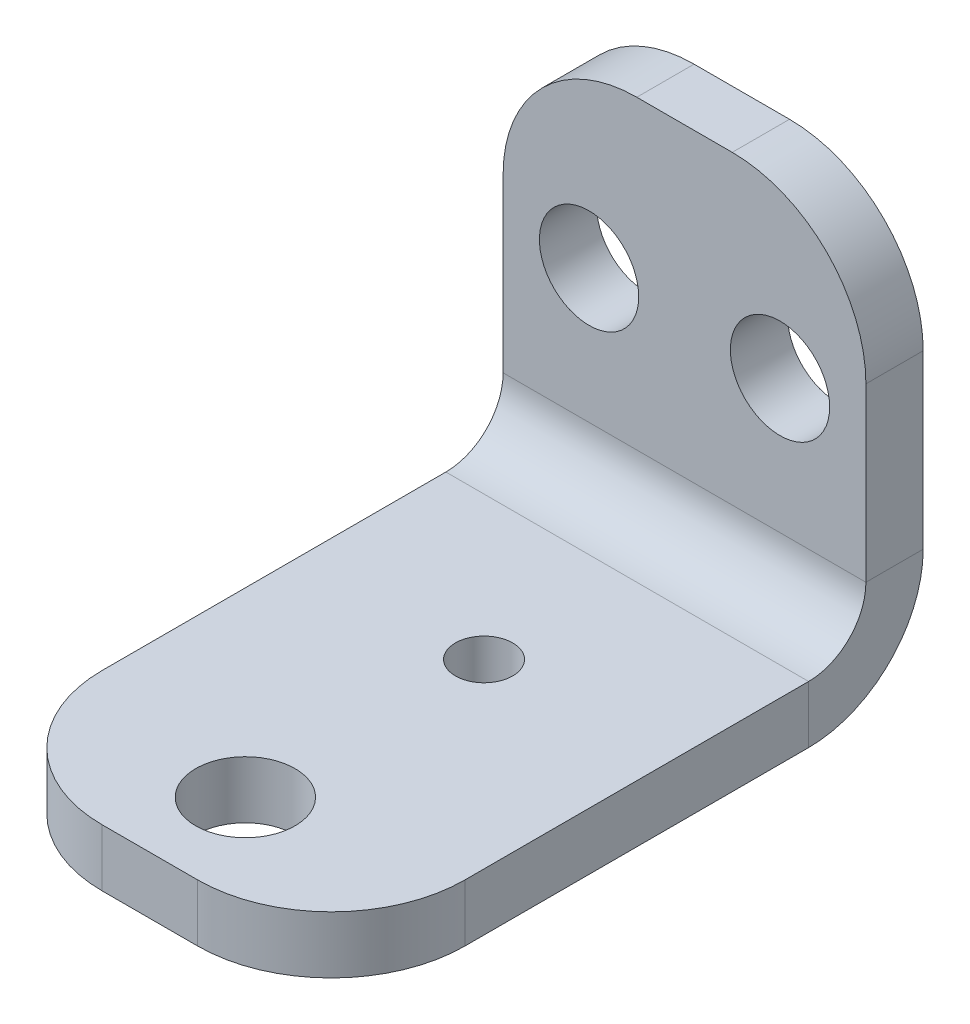
SolidWorks part; units mm, degrees
note: The reader was unsure of these and kept them because the rebuilt part matched: flange length of "Edge-Flange1".
material "AISI 4340 Steel, annealed"
ref_plane "Front Plane" through (0, 0, 0) normal (0, 0, 1) x (1, 0, 0)
ref_plane "Top Plane" through (0, 0, 0) normal (0, 1, 0) x (1, 0, 0)
ref_plane "Right Plane" through (0, 0, 0) normal (1, 0, 0) x (0, 0, -1)
sketch "Sketch1" plane through (0, 0, 0) normal (0, 0, 1) x (1, 0, 0)
  line L1 (-9.5, -11) -> (9.5, -11)
  line L2 (-9.5, -11) -> (-9.5, 11)
  line L3 (-9.5, 11) -> (9.5, 11)
  line L4 (9.5, -11) -> (9.5, 11)
  line L5 (-9.5, -11) -> (9.5, 11) construction
  line L6 (-9.5, 11) -> (9.5, -11) construction
  point P0 (0, 0)
  dimension "D1" = 19
  dimension "D2" = 22
base flange "Base-Flange1" sketch "Sketch1" thickness 3 reverse thickness direction no parameters "D1"=3
edge flange "Edge-Flange1" sketch "Sketch11" flange angle 90 flange length 28 flange position material inside bend radius 3 thickness 3 relief rectangular parameters "D6"=10, "D8"=1
sketch "Sketch11" plane through (0, -11, 0) normal (0, -1, 0) x (1, 0, 0)
  line L0 (-9.5, 0) -> (9.5, 0) construction
  line L1 (-9.5, 0) -> (9.5, 0)
  line L2 (-9.5, 0) -> (-9.5, 28)
  line L3 (-9.5, 28) -> (9.5, 28)
  line L4 (9.5, 28) -> (9.5, 0)
bend "EdgeBend2" bend radius 3 bend angle 90 parameters "D5"=2
sketch "Sketch12" plane through (0, 0, 0) normal (0, 0, 1) x (1, 0, 0)
  line L0 (0, 6.9893) -> (0, -6.026) construction
  line L3 (9.5, -5) -> (-9.5, -5) construction
  circle A0 centre (5, 2) radius 2.6
  circle A1 centre (-5, 2) radius 2.6
  dimension "D2" = 5.2
  dimension "D1" = 5
  dimension "D3" = 7
extrude "Cut-Extrude1" cut sketch "Sketch12" against normal blind 10 normal cut yes
sketch "Sketch13" plane through (0, -8, 0) normal (0, 1, 0) x (1, 0, 0)
  line L0 (0, -28) -> (0, -3) construction
  line L1 (-9.5, -3) -> (9.5, -3) construction
  line L2 (9.5, -28) -> (-9.5, -28) construction
  circle A0 centre (0, -23) radius 2.6
  dimension "D1" = 5.2
  dimension "D3" = 5
extrude "Cut-Extrude2" cut sketch "Sketch13" against normal through all normal cut yes
fillet "Fillet1" radius 7 4 edges at (9.5, -9.5, 28) (-9.5, -9.5, 28) (-9.5, 11, -1.5) (9.5, 11, -1.5)
sketch "Sketch14" plane through (0, -8, 0) normal (0, 1, 0) x (1, 0, 0)
  line L0 (-9.5, -19.025) -> (9.5, -19.025) construction
  line L1 (9.5, -3) -> (9.5, -21) construction
  line L2 (-9.5, -21) -> (-9.5, -3) construction
  line L3 (-1007.0598, -5) -> (48992.9402, -5) construction
  line L4 (-9.5, 0) -> (-2.5, 0) construction
  line L5 (-9.5, -7) -> (9.5, -7) construction
  circle A0 centre (0, -10.5) radius 1.5
  circle A3 centre (0, -10.5) radius 3.5 construction
  circle A4 centre (0, -23) radius 3.975 construction
  point P5 (0, -19.025)
  point P22 (0, -7)
  dimension "D2" = 3
  dimension "D3" = 7
  dimension "D4" = 7.95
  dimension "D1" = 5
  dimension "D5" = 2
extrude "Cut-Extrude3" cut sketch "Sketch14" against normal through all normal cut yes
sketch "Bend-Lines1" [suppressed] plane through (0, 0, 0) normal (0, 1, 0) x (1, 0, 0)
sketch "Bounding-Box1" [suppressed] plane through (0, 0, 0) normal (0, 1, 0) x (1, 0, 0)
sheet metal parameters "Sheet-Metal1" thickness 3 parameters "D1"=3
flat pattern "Flat-Pattern1" [suppressed]
sketch "Bend-Lines2" plane through (0, 0, 0) normal (0, 1, 0) x (1, 0, 0)
sketch3d "Bounding-Box2" [suppressed]
  line L0 (-12.5, 12.5, 0) -> (-12.5, -12.5, 0) construction
  line L1 (12.5, 12.5, 0) -> (12.5, -12.5, 0) construction
  line L2 (-12.5, 12.5, 0) -> (12.5, 12.5, 0) construction
  line L3 (-12.5, -12.5, 0) -> (12.5, -12.5, 0) construction
sheet metal parameters "Sheet-Metal2" thickness 3 parameters "D1"=3
flat pattern "Flat-Pattern1"
sketch "Bend-Lines2" plane through (0, 0, 0) normal (0, 0, 1) x (1, 0, 0)
  line L0 (-12.5, -10.0343) -> (12.5, -10.0343) construction
  line L1 (12.5, 10.0343) -> (-12.5, 10.0343) construction
  line L2 (-12.5, -10.0343) -> (12.5, -10.0343) construction
  line L3 (12.5, 10.0343) -> (-12.5, 10.0343) construction
sketch3d "Bounding-Box2" [suppressed]
  line L0 (12.5, 40.5686, 0) -> (12.5, -40.5686, 0) construction
  line L1 (-12.5, 40.5686, 0) -> (-12.5, -40.5686, 0) construction
  line L2 (12.5, 40.5686, 0) -> (-12.5, 40.5686, 0) construction
  line L3 (12.5, -40.5686, 0) -> (-12.5, -40.5686, 0) construction
bend of the flat pattern "Flatten-<EdgeBend2>1"
sheet metal parameters "Sheet-Metal3" thickness 3 parameters "D1"=3
flat pattern "Flat-Pattern1"
sketch "Bend-Lines2" plane through (0, 0, 0) normal (0, 0, 1) x (1, 0, 0)
  line L0 (-12.5, -10.0343) -> (12.5, -10.0343) construction
  line L1 (12.5, 10.0343) -> (-12.5, 10.0343) construction
  line L2 (-12.5, -10.0343) -> (12.5, -10.0343) construction
  line L3 (12.5, 10.0343) -> (-12.5, 10.0343) construction
sketch3d "Bounding-Box2" [suppressed]
  line L0 (12.5, 40.5686, 0) -> (12.5, -40.5686, 0) construction
  line L1 (-12.5, 40.5686, 0) -> (-12.5, -40.5686, 0) construction
  line L2 (12.5, 40.5686, 0) -> (-12.5, 40.5686, 0) construction
  line L3 (12.5, -40.5686, 0) -> (-12.5, -40.5686, 0) construction
bend of the flat pattern "Flatten-<EdgeBend2>1"
sheet metal parameters "Sheet-Metal4" thickness 3 parameters "D1"=3
flat pattern "Flat-Pattern1"
sketch "Bend-Lines2" plane through (0, 0, 0) normal (0, 0, 1) x (1, 0, 0)
  line L0 (-9.5, -8.5343) -> (9.5, -8.5343) construction
  line L2 (-9.5, -8.5343) -> (9.5, -8.5343) construction
sketch3d "Bounding-Box2" [suppressed]
  line L0 (9.5, -37.0686, 0) -> (9.5, 11, 0) construction
  line L1 (-9.5, -37.0686, 0) -> (-9.5, 11, 0) construction
  line L2 (9.5, -37.0686, 0) -> (-9.5, -37.0686, 0) construction
  line L3 (9.5, 11, 0) -> (-9.5, 11, 0) construction
bend of the flat pattern "Flatten-<EdgeBend2>1"
sheet metal parameters "Sheet-Metal5" thickness 3 parameters "D1"=3
flat pattern "Flat-Pattern1"
sketch "Bend-Lines2" plane through (0, 0, 0) normal (0, 0, 1) x (1, 0, 0)
  line L0 (-9.5, -8.5343) -> (9.5, -8.5343) construction
  line L2 (-9.5, -8.5343) -> (9.5, -8.5343) construction
sketch3d "Bounding-Box2" [suppressed]
  line L0 (9.5, -37.0686, 0) -> (9.5, 11, 0) construction
  line L1 (-9.5, -37.0686, 0) -> (-9.5, 11, 0) construction
  line L2 (9.5, -37.0686, 0) -> (-9.5, -37.0686, 0) construction
  line L3 (9.5, 11, 0) -> (-9.5, 11, 0) construction
bend of the flat pattern "Flatten-<EdgeBend2>1"
